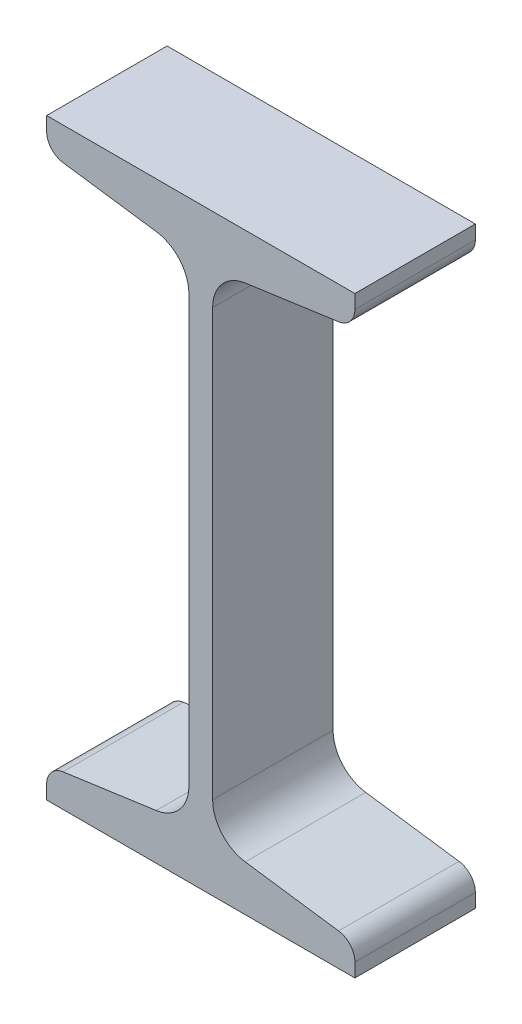
SolidWorks part; units mm, degrees
ref_plane "Front Plane" through (0, 0, 0) normal (0, 0, 1) x (1, 0, 0)
ref_plane "Top Plane" through (0, 0, 0) normal (0, 1, 0) x (1, 0, 0)
ref_plane "Right Plane" through (0, 0, 0) normal (1, 0, 0) x (0, 0, -1)
sketch "Sketch1" plane through (0, 0, 0) normal (0, 0, 1) x (1, 0, 0)
  line L0 (0, 72.9931) -> (0, -63.9253) construction
  line L1 (-32.5, 62.5) -> (32.5, 62.5)
  line L2 (-32.5, 62.5) -> (-32.5, 59.5853)
  line L3 (-32.5, -62.5) -> (32.5, -62.5)
  line L4 (32.5, -59.5853) -> (32.5, -62.5)
  line L5 (-42.3074, 0) -> (60.8749, 0) construction
  line L6 (-32.5, -59.5853) -> (-32.5, -62.5)
  line L7 (-29.0567, 55.6242) -> (-9.3866, 52.8597)
  line L8 (29.0567, -55.6242) -> (9.3866, -52.8597)
  line L9 (-29.0567, -55.6242) -> (-9.3866, -52.8597)
  line L10 (-2.5, 44.9376) -> (-2.5, -44.9376)
  line L11 (2.5, 44.9376) -> (2.5, -44.9376)
  line L12 (29.0567, 55.6242) -> (9.3866, 52.8597)
  line L13 (32.5, 62.5) -> (32.5, 59.5853)
  line L14 (-32.5, 21.4066) -> (-2.5, 21.4066) construction
  line L15 (-17.5, 62.5) -> (-17.5, 54) construction
  line L16 (-17.5, 54) -> (-17.5, 21.4066) construction
  arc A0 (-9.3866, 52.8597) -> (-2.5, 44.9376) centre (-10.5, 44.9376) cw
  arc A1 (-9.3866, -52.8597) -> (-2.5, -44.9376) centre (-10.5, -44.9376) ccw
  arc A2 (9.3866, -52.8597) -> (2.5, -44.9376) centre (10.5, -44.9376) cw
  arc A3 (9.3866, 52.8597) -> (2.5, 44.9376) centre (10.5, 44.9376) ccw
  arc A4 (-32.5, 59.5853) -> (-29.0567, 55.6242) centre (-28.5, 59.5853) ccw
  arc A5 (-32.5, -59.5853) -> (-29.0567, -55.6242) centre (-28.5, -59.5853) cw
  arc A6 (32.5, -59.5853) -> (29.0567, -55.6242) centre (28.5, -59.5853) ccw
  arc A7 (29.0567, 55.6242) -> (32.5, 59.5853) centre (28.5, 59.5853) ccw
  point P18 (0, -62.5)
  point P27 (0, 62.5)
  point P34 (-32.5, 56.1081)
  point P37 (-32.5, -56.1081)
  point P40 (32.5, -56.1081)
  point P43 (32.5, 56.1081)
  dimension "Radius_root" = 8
  dimension "Radius_toe" = 4
  dimension "Depth" = 125
  dimension "Width" = 65
  dimension "Web_thickness" = 5
  dimension "Thickness" = 8.5
  dimension "D1" = 98
extrude "BaseSection" add sketch "Sketch1" along normal mid plane 25.4
